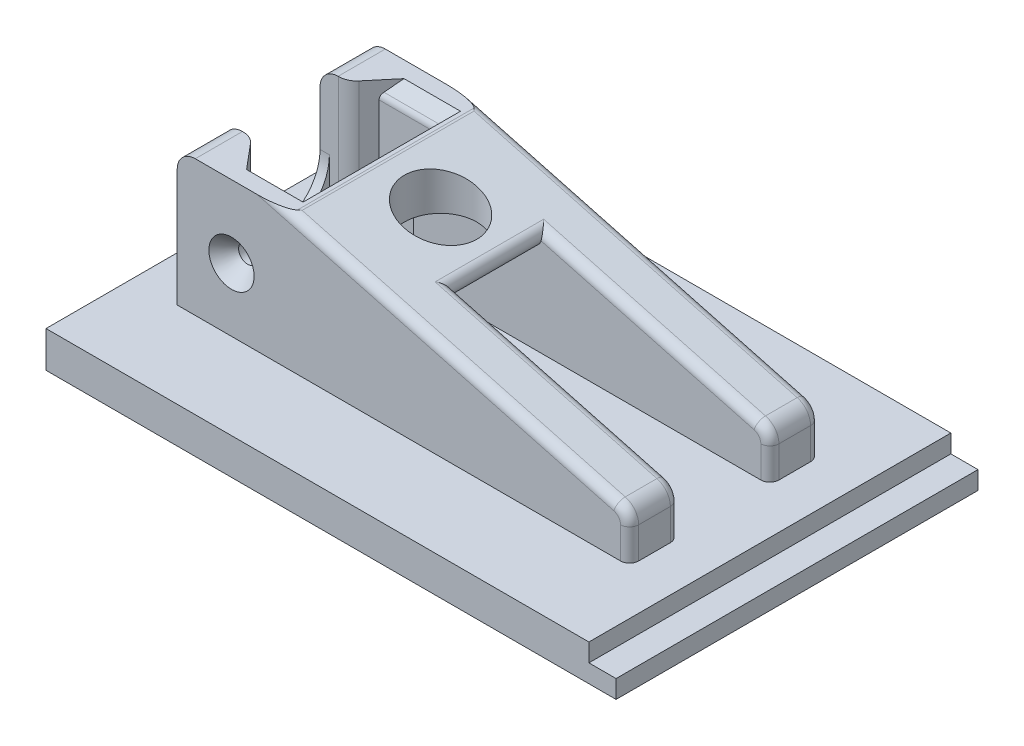
SolidWorks part; units mm, degrees
ref_plane "Ebene vorne" through (0, 0, 0) normal (0, 0, 1) x (1, 0, 0)
ref_plane "Ebene oben" through (0, 0, 0) normal (0, 1, 0) x (1, 0, 0)
ref_plane "Ebene rechts" through (0, 0, 0) normal (1, 0, 0) x (0, 0, -1)
sketch "Skizze1" plane through (0, 0, 0) normal (0, 1, 0) x (1, 0, 0)
  line L0 (0, 0) -> (60, 0)
  line L1 (-55, 0) -> (55, 0) construction
  line L2 (60, 0) -> (60, 40)
  line L3 (60, 40) -> (0, 40)
  line L4 (0, -55) -> (0, 55) construction
  line L5 (0, 40) -> (0, 0)
  line L6 (60, 20) -> (0, 20) construction
  line L7 (30, 0) -> (30, 40) construction
  dimension "D1" = 40
  dimension "D2" = 60
extrude "Aufsatz-Linear austragen1" add sketch "Skizze1" along normal blind 4
sketch "Skizze2" plane through (0, 4, 0) normal (0, 1, 0) x (1, 0, 0)
  line L0 (60, 20) -> (0, 20) construction
  line L1 (60, 0) -> (60, 40) construction
  line L2 (0, -2.2) -> (0, 2.2) construction
  line L3 (30, 20) -> (30, 0) construction
  line L4 (-2.2, 0) -> (2.2, 0) construction
  line L5 (30, 20) -> (30, 40) construction
  line L6 (60, 40) -> (0, 40) construction
  line L7 (55, 30.5) -> (55, 9.5)
  line L8 (55, 9.5) -> (5, 9.5)
  line L9 (5, 9.5) -> (5, 30.5)
  line L10 (55, 30.5) -> (5, 30.5)
  point P18 (5, 20)
  point P19 (55, 20)
  dimension "D1" = 50
  dimension "D2" = 21
  dimension "D3" = 5
extrude "Aufsatz-Linear austragen2" add sketch "Skizze2" along normal blind 15
sketch "Skizze3" plane through (0, 19, 0) normal (0, 1, 0) x (1, 0, 0)
  line L0 (55, 20) -> (5, 20) construction
  line L1 (55, 9.5) -> (55, 30.5) construction
  line L2 (5, 30.5) -> (5, 9.5) construction
  line L3 (30, 30.5) -> (30, 9.5) construction
  line L4 (55, 30.5) -> (5, 30.5) construction
  line L5 (5, 9.5) -> (55, 9.5) construction
  line L6 (15.607, 12.8) -> (15.607, 27.2)
  line L7 (15.607, 12.8) -> (9.607, 12.8)
  line L8 (9.607, 12.8) -> (8, 14.7151)
  line L9 (8, 14.7151) -> (5, 14.7151)
  line L10 (5, 30.5) -> (5, 9.5) construction
  line L11 (8, 25.2849) -> (5, 25.2849)
  line L12 (9.607, 27.2) -> (8, 25.2849)
  line L13 (15.607, 27.2) -> (9.607, 27.2)
  point P23 (15.607, 20)
  dimension "D1" = 7.2
  dimension "D2" = 6
  dimension "D3" = 130
  dimension "D4" = 3
  dimension "D5" = 2.5
extrude "Schnitt-Linear austragen1" cut sketch "Skizze3" against normal blind 15 and the other way through all
fillet "Verrundung2" radius 2 2 edges at (8, 11.5, -25.2849) (8, 11.5, -14.7151)
sketch "Skizze10" plane through (0, 4, 0) normal (0, 1, 0) x (1, 0, 0)
  line L0 (5, 25.2849) -> (5, 14.7151)
  line L1 (5, 14.7151) -> (6.0337, 14.7151)
  line L2 (7.0674, 14.7151) -> (5, 14.7151) construction
  line L3 (6.0337, 14.7151) -> (6.0337, 25.2849)
  line L4 (5, 25.2849) -> (7.0674, 25.2849) construction
  line L5 (6.0337, 25.2849) -> (5, 25.2849)
extrude "Aufsatz-Linear austragen4" add sketch "Skizze10" along normal blind 7
sketch "Skizze12" plane through (5, 0, 0) normal (-1, 0, 0) x (0, 0, 1)
  line L0 (-25.2849, 11) -> (-14.7151, 11) construction
  circle A0 centre (-20, 11) radius 5.2849
extrude "Schnitt-Linear austragen4" cut sketch "Skizze12" against normal blind 3
chamfer "Fase6" distance 1.5 angle 45 1 edges at (15.607, 19, -20)
fillet "Verrundung7" radius 1 1 edges at (15.607, 17.5, -20)
fillet "Verrundung8" radius 2 2 edges at (5, 19, -12.1076) (5, 19, -27.8924)
chamfer "Fase7" distance 1.5 angle 45 2 edges at (13.357, 19, -12.8) (13.357, 19, -27.2)
fillet "Verrundung9" radius 1 2 edges at (12.6519, 17.5, -27.2) (12.6519, 17.5, -12.8)
sketch "Skizze15" plane through (0, 0, -30.5) normal (0, 0, -1) x (-1, 0, 0)
  line L0 (-5, 17) -> (-5, 4) construction
  line L1 (-60, 4) -> (0, 4) construction
  circle A0 centre (-11, 11) radius 1
  dimension "D1" = 2
  dimension "D2" = 7
  dimension "D3" = 6
extrude "Fixierbohrungen" cut sketch "Skizze15" against normal up to surface (21 mm away) up to face at (25.3172, 12.6828, -9.5)
sketch "Skizze16" plane through (0, 4, 0) normal (0, 1, 0) x (1, 0, 0)
  line L0 (15.607, 27.2) -> (15.607, 20.2)
  line L1 (15.607, 27.2) -> (15.607, 12.8) construction
  line L2 (15.607, 20.2) -> (11.607, 20.2)
  line L4 (9.607, 27.2) -> (15.607, 27.2) construction
  line L6 (11.607, 20.2) -> (11.607, 27.2)
  line L7 (15.607, 27.2) -> (11.607, 27.2)
  dimension "D1" = 7
  dimension "D2" = 4
extrude "Kabelschacht" cut sketch "Skizze16" against normal up to surface (4 mm away) up to face at (30, 0, -20)
chamfer "Fase_Bohrung" distance 1.5 angle 50 2 edges at (10, 11, -30.5) (10, 11, -9.5) first distance on face at (10, 11, -30.5) first distance on face at (10, 11, -9.5)
sketch "Skizze17" plane through (60, 0, 0) normal (1, 0, 0) x (0, 0, -1)
  line L0 (0, 0) -> (40, 0)
  line L1 (22, 0) -> (-22, 0) construction
  line L2 (40, 4) -> (40, 0) construction
  line L3 (40, 0) -> (40, 2)
  line L4 (40, 2) -> (0, 2)
  line L5 (0, 10.45) -> (0, -10.45) construction
  line L6 (0, 2) -> (0, 0)
  dimension "D1" = 2
extrude "Aufsatz-Linear austragen5" add sketch "Skizze17" along normal blind 3
sketch "Skizze19" plane through (15.607, 0, 0) normal (-1, 0, 0) x (0, 0, 1)
  line L0 (-20, 17.0858) -> (-20, 0) construction
  line L1 (-12.8, 17.0858) -> (-27.2, 17.0858) construction
  line L2 (22, 0) -> (-22, 0) construction
  line L3 (-25, 4) -> (-15, 4)
  line L4 (-15, 4) -> (-15, 14)
  line L5 (-15, 14) -> (-25, 14)
  line L6 (-25, 4) -> (-25, 14)
  line L7 (-20.2, 4) -> (-12.8, 4) construction
  point P11 (-20, 14)
  point P12 (-20, 4)
  dimension "D1" = 5
  dimension "D2" = 10
  dimension "D3" = 0
extrude "Schnitt-Linear austragen5" cut sketch "Skizze19" against normal up to surface (39.393 mm away) up to face at (55, 11.5, -20)
chamfer "Fase8" distance 10 angle 75 1 edges at (55, 19, -20) first distance on face at (55, 10.25, -20)
fillet "Verrundung16" radius 2 2 edges at (55, 9, -27.75) (55, 9, -12.25)
fillet "Verrundung17" radius 1 14 edges at (55, 5.7327, -15) (54.5867, 8.6829, -15) (55, 5.7327, -9.5) (54.5867, 8.6829, -9.5) (55, 5.7327, -30.5) (54.5867, 8.6829, -30.5) (55, 5.7327, -25) (54.5867, 8.6829, -25) (36.3397, 14, -20) (44.9287, 11.6986, -15) (35.5986, 14.1986, -9.5) (17.6795, 19, -20) (35.5986, 14.1986, -30.5) (44.9287, 11.6986, -25)
sketch "Skizze21" plane through (0, 14, 0) normal (0, -1, 0) x (1, 0, 0)
  line L0 (15.607, -15) -> (15.607, -25) construction
  line L1 (28.744, -15) -> (15.607, -15) construction
  circle A0 centre (23.607, -20) radius 4
  dimension "D1" = 8
  dimension "D2" = 8
  dimension "D3" = 5
extrude "Schnitt-Linear austragen6" cut sketch "Skizze21" against normal up to surface (3.4117 mm away) up to face at (38.4612, 13.4316, -20)
